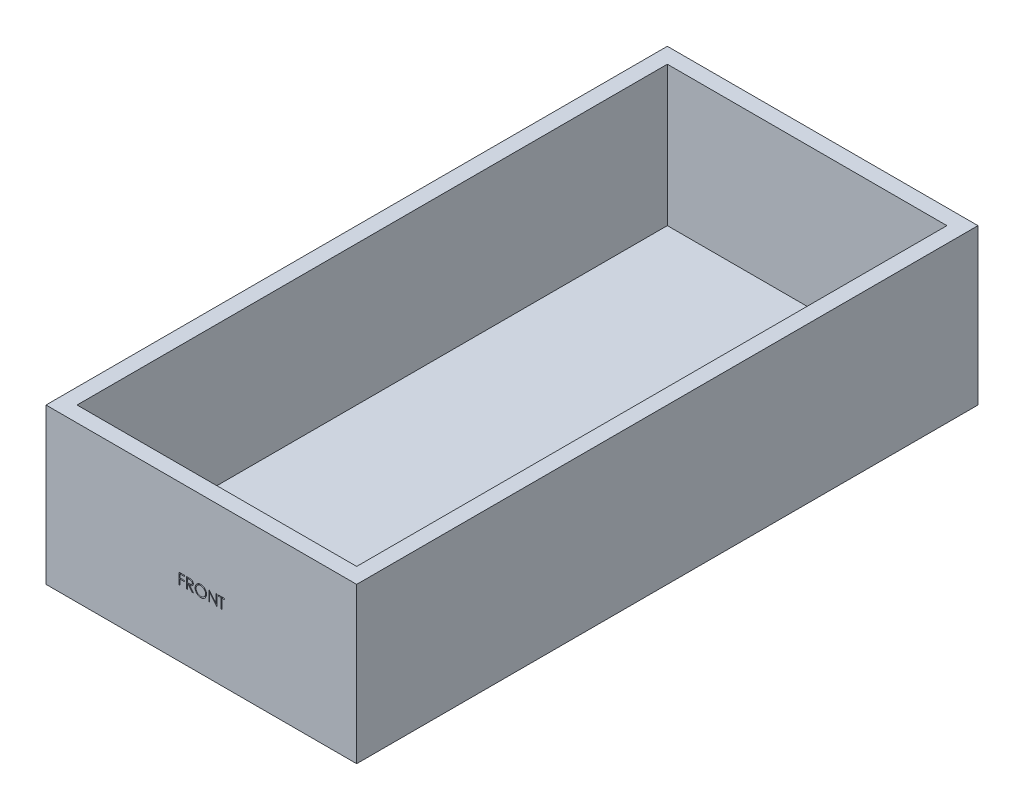
SolidWorks part; units mm, degrees
material "ABS"
ref_plane "Front Plane" through (0, 0, 0) normal (0, 0, 1) x (1, 0, 0)
ref_plane "Top Plane" through (0, 0, 0) normal (0, 1, 0) x (1, 0, 0)
ref_plane "Right Plane" through (0, 0, 0) normal (1, 0, 0) x (0, 0, -1)
ref_axis "X" through (-88.99, 0, 0) along (1, 0, 0)
ref_axis "Y" through (0, 55, 0) along (0, -1, 0)
ref_axis "Z" through (0, 0, -88.99) along (0, 0, 1)
sketch "Sketch1" plane through (0, 0, 0) normal (0, 1, 0) x (1, 0, 0)
  line L1 (-50, 100) -> (50, 100)
  line L2 (-50, 100) -> (-50, -100)
  line L3 (-50, -100) -> (50, -100)
  line L4 (50, 100) -> (50, -100)
  line L5 (-50, 100) -> (50, -100) construction
  line L6 (-50, -100) -> (50, 100) construction
  point P0 (0, 0)
  dimension "D1" = 200
  dimension "D2" = 100
extrude "Boss-Extrude1" add sketch "Sketch1" along normal blind 50
shell "Shell1" thickness 5 removed face at (0, 50, 0)
sketch "Sketch2" plane through (0, 0, 100) normal (0, 0, 1) x (1, 0, 0)
  text T0 "FRONT"
extrude "Cut-Extrude1" cut sketch "Sketch2" against normal blind 1
